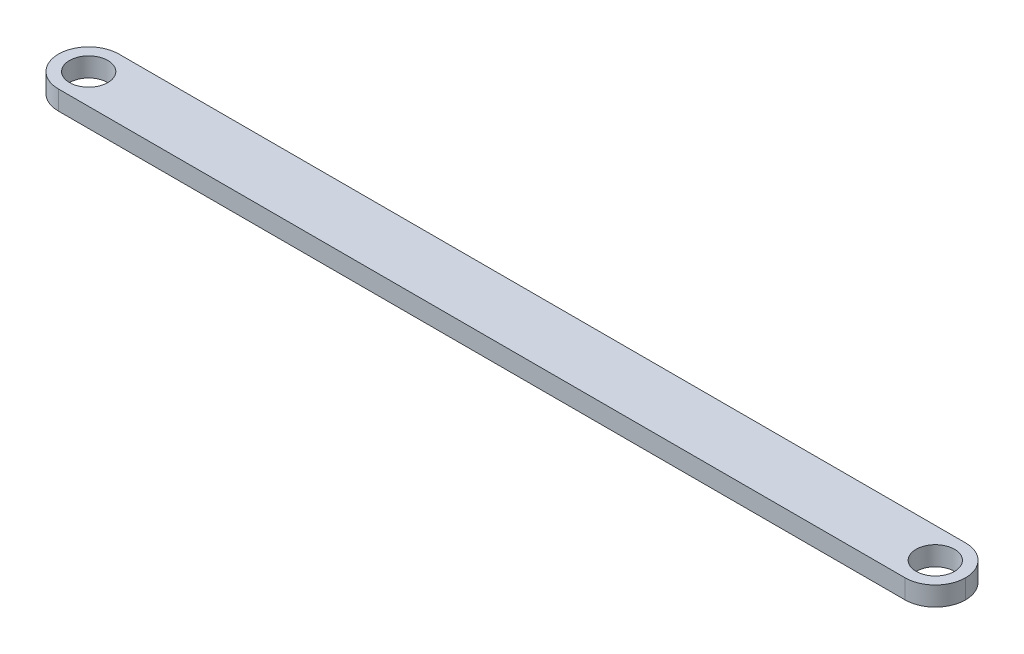
SolidWorks part; units mm, degrees
material "ABS"
ref_plane "Front Plane" through (0, 0, 0) normal (0, 0, 1) x (1, 0, 0)
ref_plane "Top Plane" through (0, 0, 0) normal (0, 1, 0) x (1, 0, 0)
ref_plane "Right Plane" through (0, 0, 0) normal (1, 0, 0) x (0, 0, -1)
sketch "Sketch1" plane through (0, 0, 0) normal (0, 1, 0) x (1, 0, 0)
  line L1 (-150, 10) -> (150, 10)
  line L2 (-150, 10) -> (-150, -10)
  line L3 (-150, -10) -> (150, -10)
  line L4 (150, 10) -> (150, -10)
  point P4 (0, -10)
  point P5 (0, 10)
  point P9 (150, 0)
  dimension "D1" = 300
  dimension "D2" = 20
extrude "Boss-Extrude1" add sketch "Sketch1" along normal blind 6.35
sketch "Sketch2" plane through (0, 0, 0) normal (0, -1, 0) x (-1, 0, 0)
  line L0 (-3.4925, 0) -> (3.4925, 0) construction
  line L1 (150, 10) -> (150, -10) construction
  circle A0 centre (140, 0) radius 6.35
  dimension "D1" = 12.7
  dimension "D2" = 10
extrude "Cut-Extrude1" cut sketch "Sketch2" against normal up to surface (6.35 mm away) up to face at (0, 6.35, 0)
mirror "Mirror1" about plane through (0, 0, 0) normal (1, 0, 0) of "Cut-Extrude1"
fillet "Congé1" radius 10 4 edges at (-150, 3.175, -10) (-150, 3.175, 10) (150, 3.175, -10) (150, 3.175, 10)
